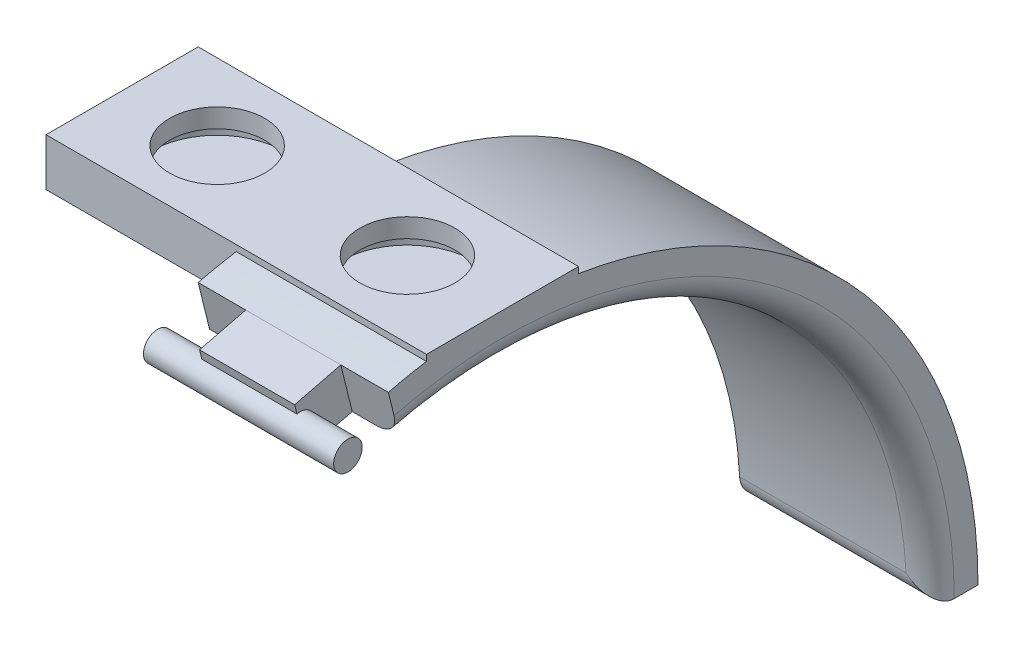
SolidWorks part; units mm, degrees
ref_plane "Front Plane" through (0, 0, 0) normal (0, 0, 1) x (1, 0, 0)
ref_plane "Top Plane" through (0, 0, 0) normal (0, 1, 0) x (1, 0, 0)
ref_plane "Right Plane" through (0, 0, 0) normal (1, 0, 0) x (0, 0, -1)
sketch "Sketch2" plane through (0, 0, 0) normal (1, 0, 0) x (0, 0, -1)
  line L0 (-50, 0) -> (-45, 0)
  line L1 (45, 0) -> (50, 0)
  arc A0 (45, 0) -> (-45, 0) centre (0, 0) ccw
  arc A1 (50, 0) -> (-50, 0) centre (0, 0) ccw
  dimension "D1" = 45
  dimension "D2" = 50
extrude "Boss-Extrude1" add sketch "Sketch2" along normal blind 20
sketch "Sketch3" plane through (0, 0, 0) normal (1, 0, 0) x (0, 0, -1)
  line L0 (0, 45) -> (8, 45)
  line L1 (8, 45) -> (8, 50)
  line L2 (8, 50) -> (-8, 50)
  line L3 (-8, 50) -> (-8, 45)
  line L4 (-8, 45) -> (0, 45)
  arc A0 (45, 0) -> (-45, 0) centre (0, 0) ccw construction
  dimension "D1" = 8
  dimension "D2" = 16
extrude "Boss-Extrude2" add sketch "Sketch3" along normal blind 20 and the other way blind 20
sketch "Sketch4" plane through (0, 50, 0) normal (0, 1, 0) x (1, 0, 0)
  circle A0 centre (10, 0) radius 5
  dimension "D1" = 10
extrude "Cut-Extrude1" cut sketch "Sketch4" against normal blind 2
sketch "Sketch5" plane through (0, 48, 0) normal (0, 1, 0) x (1, 0, 0)
  circle A0 centre (10, 0) radius 7
  dimension "D1" = 14
extrude "Cut-Extrude2" cut sketch "Sketch5" against normal blind 2
sketch "Sketch15" plane through (0, 0, 0) normal (-1, 0, 0) x (0, 0, 1)
  line L0 (0, 0) -> (12, 48.5386) construction
  arc A0 (50, 0) -> (8, 49.3559) centre (0, 0) ccw construction
  arc A1 (50, 0) -> (12, 48.5386) centre (0, 0) ccw
  dimension "D1" = 12
sketch "Sketch16" plane through (0, 0, 0) normal (0, -1, 0) x (1, 0, 0)
  line L1 (0, 50) -> (20, 50)
  line L2 (0, 50) -> (0, 45)
  line L3 (0, 45) -> (20, 45)
  line L4 (20, 50) -> (20, 45)
sweep "Cut-Sweep1" cut profiles "Sketch16" path "Sketch15"
sketch "Sketch17" plane through (0, 0, 0) normal (0, -0.24, 0.9708) x (1, 0, 0)
  line L0 (0, 45) -> (20, 45) construction
  line L1 (10, 45) -> (5, 45)
  line L2 (10, 45) -> (10, 50)
  line L3 (10, 50) -> (5, 50)
  line L4 (5, 45) -> (5, 50)
  line L5 (20, 50) -> (0, 50) construction
  dimension "D1" = 5
extrude "Boss-Extrude10" add sketch "Sketch17" along normal blind 5
sketch "Sketch18" plane through (10, 0, 0) normal (1, 0, 0) x (0, 0, -1)
  line L0 (-15.6539, 42.4848) -> (-16.8539, 47.3386) construction
  circle A0 centre (-16.2539, 44.9117) radius 1.5
  dimension "D1" = 3
extrude "Boss-Extrude11" add sketch "Sketch18" against normal blind 10
mirror "Mirror1" about plane through (10, 42.4848, 15.6539) normal (-1, 0, 0) of "Boss-Extrude11", "Boss-Extrude10"
sketch "Sketch19" plane through (0, 50, 0) normal (0, 1, 0) x (1, 0, 0)
  line L0 (-20, 8) -> (20, 8) construction
  line L1 (-20, 8) -> (-20, -8) construction
  circle A0 centre (-10, 0) radius 5
  dimension "D1" = 10
  dimension "D2" = 8
  dimension "D3" = 10
extrude "Cut-Extrude3" cut sketch "Sketch19" against normal blind 2
sketch "Sketch20" plane through (0, 48, 0) normal (0, 1, 0) x (1, 0, 0)
  circle A0 centre (-10, 0) radius 7
  dimension "D1" = 14
extrude "Cut-Extrude4" cut sketch "Sketch20" against normal blind 2
fillet "Fillet2" radius 2.5 2 edges at (20, 35.433, -27.7399) (10, 0, -45)
